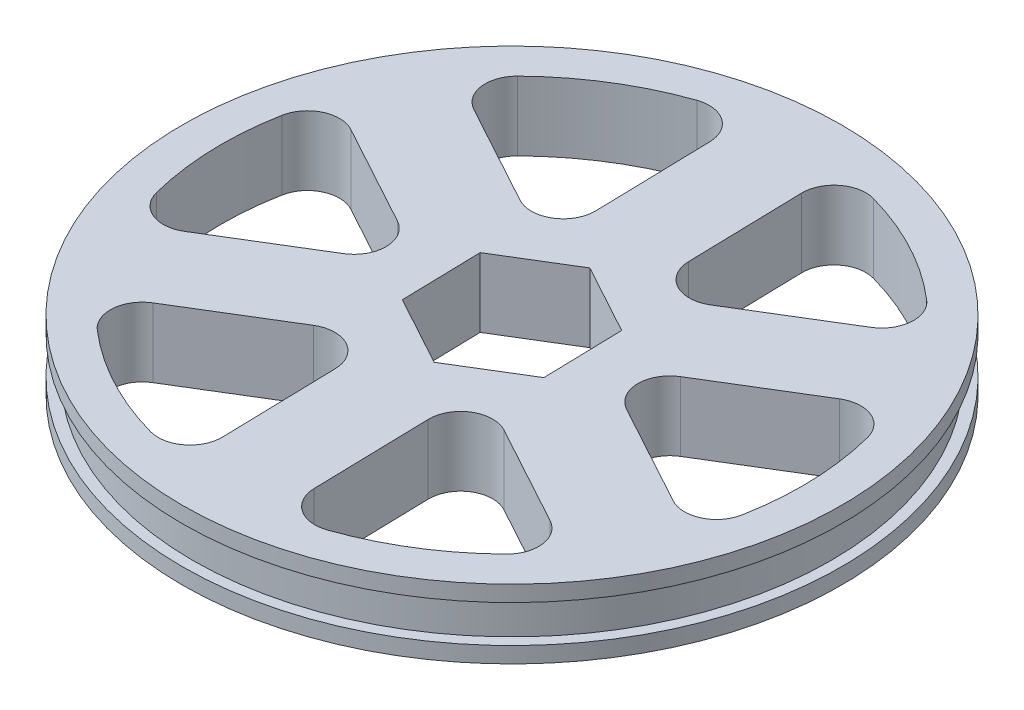
SolidWorks part; units mm, degrees
ref_plane "Front Plane" through (0, 0, 0) normal (0, 0, 1) x (1, 0, 0)
ref_plane "Top Plane" through (0, 0, 0) normal (0, 1, 0) x (1, 0, 0)
ref_plane "Right Plane" through (0, 0, 0) normal (1, 0, 0) x (0, 0, -1)
sketch "Sketch1" plane through (0, 0, 0) normal (0, 1, 0) x (1, 0, 0)
  circle A0 centre (0, 0) radius 31
  circle A1 centre (0, 0) radius 30
extrude "Boss-Extrude1" add sketch "Sketch1" along normal blind 6.5 contours A1
extrude "Boss-Extrude3" add sketch "Sketch1<4>" along normal blind 1.5
sketch "Sketch1<4>" plane through (0, 0, 0) normal (0, 1, 0) x (1, 0, 0) same geometry as "Sketch1"
sketch "Sketch4" plane through (0, 6.5, 0) normal (0, 1, 0) x (1, 0, 0)
  circle A0 centre (0, 0) radius 31
extrude "Boss-Extrude4" add sketch "Sketch4" against normal blind 1.5
sketch "Sketch6" plane through (0, 6.5, 0) normal (0, 1, 0) x (1, 0, 0)
  line L1 (-6.5891, 3.5941) -> (-6.4071, -3.9093)
  line L2 (-6.4071, -3.9093) -> (0.182, -7.5033)
  line L3 (0.182, -7.5033) -> (6.5891, -3.5941)
  line L4 (6.5891, -3.5941) -> (6.4071, 3.9093)
  line L5 (6.4071, 3.9093) -> (-0.182, 7.5033)
  line L6 (-0.182, 7.5033) -> (-6.5891, 3.5941)
  circle A0 centre (0, 0) radius 6.5 construction
extrude "Cut-Extrude1" cut sketch "Sketch6" against normal through all
sketch "Sketch7" plane through (0, 6.5, 0) normal (0, 1, 0) x (1, 0, 0)
  line L2 (-4.4273, 7.256) -> (-21.8367, 16.7521)
  line L3 (-4.4273, 7.256) -> (-4.9123, 27.2501)
  arc A0 (-21.8367, 16.7521) -> (-4.9123, 27.2501) centre (0.4198, -0.2375) cw
  dimension "D1" = 60
extrude "Cut-Extrude2" cut sketch "Sketch7" against normal through all contours L3 A0 L2
fillet "Fillet1" radius 3 3 edges at (-4.4273, 3.25, -7.256) (-4.9123, 3.25, -27.2501) (-21.8367, 3.25, -16.7521)
pattern_circular "CirPattern1" count 6 every 60 about axis through (0, 6.5, 0) along (0, 1, 0) of "Cut-Extrude2", "Fillet1"
